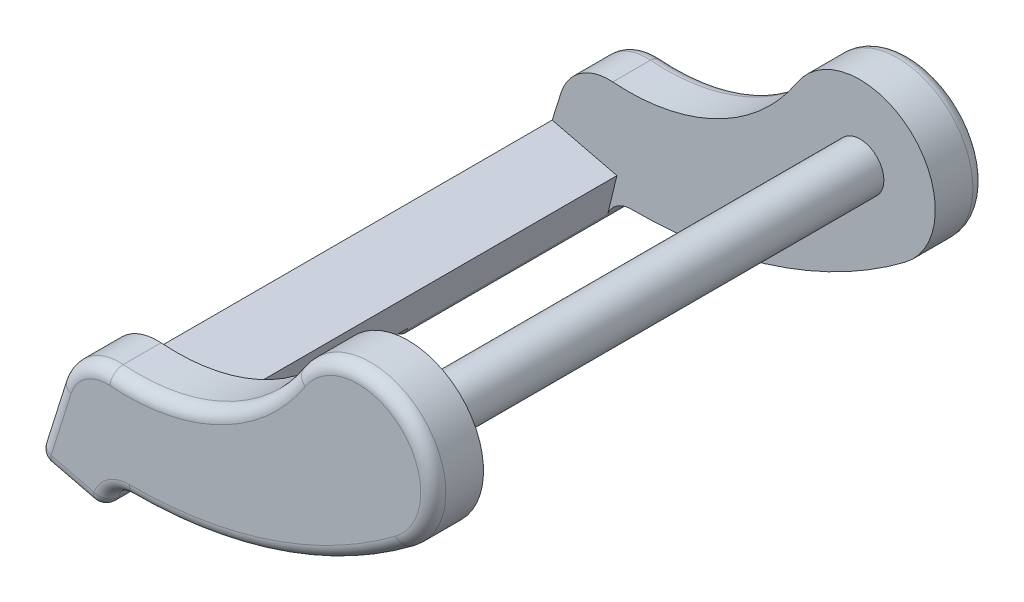
SolidWorks part; units mm, degrees
ref_plane "Front" through (0, 0, 0) normal (0, 0, 1) x (1, 0, 0)
ref_plane "Top" through (0, 0, 0) normal (0, 1, 0) x (1, 0, 0)
ref_plane "Right" through (0, 0, 0) normal (1, 0, 0) x (0, 0, -1)
sketch "Sketch1" plane through (0, 0, 0) normal (0, 0, 1) x (1, 0, 0)
  line L0 (-8.1853, -56.5205) -> (-10.8636, -55.8705)
  line L1 (-7.8459, -55.4405) -> (-8.1853, -56.5205)
  line L2 (-10.8636, -55.8705) -> (-9.908, -52.83)
  arc A0 (3.8077, -51.824) -> (-0.5196, -47.8013) centre (2, -49.4297) ccw
  arc A1 (3.8077, -51.824) -> (-7.8459, -55.4405) centre (-7.0384, -37.4587) cw
  arc A2 (-0.5196, -47.8013) -> (-7.8477, -51.4355) centre (-7.2384, -43.4588) cw
  arc A3 (-7.8477, -51.4355) -> (-9.908, -52.83) centre (-8, -53.4297) ccw
  dimension "D1" = 6
  dimension "D2" = 4
  dimension "D3" = 10
  dimension "D4" = 4
  dimension "D8" = 8
  dimension "D9" = 18
  dimension "D5" = 2.75
extrude "Base-Extrude" add sketch "Sketch1" along normal mid plane 22
shell "Shell1" thickness 2 removed face at (-1.8612, -54.141, 0) removed face at (2.8433, -48.5226, 0) removed face at (-3.9338, -50.1221, 0) removed face at (-8.9994, -51.9531, 0) removed face at (-10.3858, -54.3503, 0)
fillet "Fillet3" radius 1 1 edges at (-7.8459, -55.4405, 0)
fillet "Fillet4" radius 0.5 2 edges at (-8.1853, -56.5205, 0) (-10.8636, -55.8705, 0)
fillet "Fillet6" radius 0.5 18 edges at (-1.3545, -54.5377, -11) (4.0426, -47.2325, -11) (-3.684, -50.6258, -11) (-9.121, -51.7735, -11) (-10.3057, -54.0954, -11) (-10.6618, -55.7565, -11) (-9.4908, -56.2036, -11) (-8.2866, -56.3673, -11) (-7.6834, -55.634, -11) (-10.6618, -55.7565, 11) (-10.3057, -54.0954, 11) (-9.121, -51.7735, 11) (-3.684, -50.6258, 11) (4.0426, -47.2325, 11) (-1.3545, -54.5377, 11) (-7.6834, -55.634, 11) (-8.2866, -56.3673, 11) (-9.4908, -56.2036, 11)
sketch "Sketch2" plane through (0, 0, 9) normal (0, 0, -1) x (-1, 0, 0)
  circle A0 centre (-2, -49.4297) radius 0.95
extrude "Boss-Extrude1" add sketch "Sketch2" along normal up to surface (18 mm away) up to face at (-4.4258, -51.9628, -9)
sketch "Sketch3" plane through (-13.4082, -55.253, 0) normal (-0.2358, -0.9718, 0) x (0.9718, -0.2358, 0)
  line L0 (5.4053, 10.5) -> (5.4053, -10.5) construction
  line L1 (5.4053, 9) -> (5.4053, -9)
  line L2 (8.4699, 9) -> (8.4699, -9) construction
  line L3 (8.4699, 9) -> (8.4699, -9)
  line L4 (8.4699, 9) -> (5.4053, 9)
  line L5 (8.4699, -9) -> (5.4053, -9)
extrude "Cut-Extrude1" cut sketch "Sketch3" against normal through all
sketch "Sketch5" plane through (-13.4082, -55.253, 0) normal (-0.2358, -0.9718, 0) x (0.9718, -0.2358, 0)
  line L1 (5.8625, 0.95) -> (3.996, 0.95)
  line L2 (5.8625, -0.95) -> (5.8625, 0.95)
  line L3 (3.996, -0.95) -> (5.8625, -0.95)
  arc A0 (3.996, 0.95) -> (3.996, -0.95) centre (3.996, 0) ccw
extrude "Cut-Extrude2" cut sketch "Sketch5" against normal blind 0.5
fillet "Fillet8" radius 0.1 7 edges at (-8.2866, -56.3673, 0.95) (-9.0811, -56.3031, 0.95) (-10.0043, -56.079, 0.8118) (-10.4361, -55.9645, 0.1376) (-10.0043, -56.079, -0.8118) (-8.2866, -56.3673, -0.95) (-9.0811, -56.3031, -0.95)
